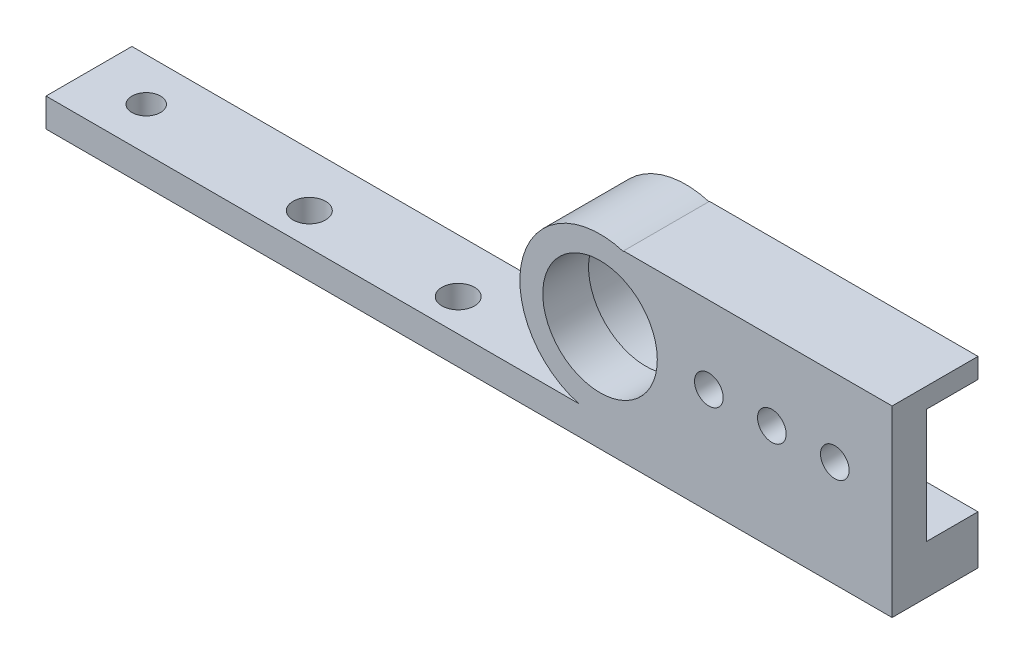
SolidWorks part; units mm, degrees
ref_plane "前视基准面" through (0, 0, 0) normal (0, 0, 1) x (1, 0, 0)
ref_plane "上视基准面" through (0, 0, 0) normal (0, 1, 0) x (1, 0, 0)
ref_plane "右视基准面" through (0, 0, 0) normal (1, 0, 0) x (0, 0, -1)
sketch "草图1" plane through (0, 0, 0) normal (0, 0, 1) x (1, 0, 0)
  line L1 (20, -10) -> (-20, -10)
  line L2 (20, -10) -> (20, 10)
  line L3 (20, 10) -> (-20, 10)
  line L4 (-20, -10) -> (-20, 10)
  line L5 (20, -10) -> (-20, 10) construction
  line L6 (20, 10) -> (-20, -10) construction
  point P0 (0, 0)
  dimension "D1" = 40
  dimension "D2" = 20
extrude "凸台-拉伸1" add sketch "草图1" along normal blind 6
sketch "草图2" plane through (0, 0, 6) normal (0, 0, 1) x (1, 0, 0)
  line L0 (20, -10) -> (20, 10) construction
  circle A0 centre (10, 0) radius 2.5
  circle A1 centre (-1, 0) radius 2.5
  circle A2 centre (-12, 0) radius 2.5
  dimension "D1" = 10
  dimension "D2" = 5
  dimension "D3" = 3
extrude "切除-拉伸1" cut sketch "草图2" against normal through all
sketch "草图3" plane through (0, 0, 6) normal (0, 0, 1) x (1, 0, 0)
  line L0 (20, 13.5) -> (20, 10)
  line L1 (20, -13.5) -> (-26.894, -13.5)
  line L3 (20, 13.5) -> (-26.894, 13.5)
  line L4 (-20, 10) -> (-20, -10)
  line L5 (-20, -10) -> (20, -10)
  line L6 (20, -10) -> (20, 10)
  line L7 (20, 10) -> (-20, 10)
  line L8 (-20, 10) -> (-20, -10)
  line L9 (-20, -10) -> (20, -10)
  line L10 (20, -10) -> (20, 10)
  line L11 (20, 10) -> (-20, 10)
  line L12 (-26.894, -13.5) -> (-26.894, 13.5)
  line L13 (20, -10.0394) -> (-26.894, 13.5) construction
  line L14 (20, 10.0394) -> (-26.894, -13.5) construction
  line L15 (20, -10) -> (20, -13.5)
  circle A0 centre (-31, 0) radius 11
  circle A1 centre (-31, 0) radius 14
  point P2 (0, 0)
  line M10 (-20, 10) -> (-20, -10)
  line M11 (-20, -10) -> (20, -10)
  line M13 (20, 10) -> (-20, 10)
  dimension "D3" = 22
  dimension "D4" = 28
  dimension "D2" = 3.5
  dimension "D1" = 0
extrude "凸台-拉伸2" add sketch "草图3" against normal blind 15 contours L3 A1 L1 L12 A0 | A1 L1 L15 M11 M10 | L1 A1 L8 A0 L12 | L8 A1 L3 L12 A0 | L8 A1 | A1 L0 L3 M10 M13 region at (-1.9449, 11.7771, 6) region at (-1.9449, -11.7771, 6) region at (-23.0173, 9.0328, 6) region at (-27.2274, 11.7946, 6) region at (-18.7882, 0, 6) region at (-23.0173, -9.0328, 6)
sketch "草图5" plane through (0, 0, 6) normal (0, 0, 1) x (1, 0, 0)
  circle A0 centre (-31, 0) radius 10
  circle A1 centre (-31, 0) radius 11 construction
  circle A2 centre (-31, 0) radius 11
  dimension "D1" = 20
extrude "凸台-拉伸3" add sketch "草图5" against normal blind 8
sketch "草图6" plane through (0, 0, 6) normal (0, 0, 1) x (1, 0, 0)
  circle A0 centre (-31, 0) radius 8.5
  circle A1 centre (-31, 0) radius 10 construction
  circle A2 centre (-31, 0) radius 10
  dimension "D1" = 17
sketch "草图9" plane through (0, -13.5, 0) normal (0, -1, 0) x (1, 0, 0)
  circle A0 centre (-18.2368, -1.344) radius 5.5352
sketch "草图10" plane through (20, 0, 0) normal (1, 0, 0) x (0, 0, -1)
  line L1 (9, -13.5) -> (-6, -13.5)
  line L2 (9, -13.5) -> (9, -18.5)
  line L3 (9, -18.5) -> (-6, -18.5)
  line L4 (-6, -13.5) -> (-6, -18.5)
  dimension "D1" = 5
extrude "凸台-拉伸4" add sketch "草图10" against normal blind 200
sketch "草图11" plane through (0, 0, 6) normal (0, 0, 1) x (1, 0, 0)
  line L1 (-28.6193, -11.8661) -> (-25.5243, -11.8661)
  line L2 (-28.6193, -11.8661) -> (-28.6193, -14.961)
  line L3 (-28.6193, -14.961) -> (-25.5243, -14.961)
  line L4 (-25.5243, -11.8661) -> (-25.5243, -14.961)
extrude "凸台-拉伸5" add sketch "草图11" against normal through all
sketch "草图13" plane through (0, -18.5, 0) normal (0, -1, 0) x (1, 0, 0)
  line L0 (-164.0842, 6) -> (-164.0842, -9)
  line L1 (-180, 6) -> (20, 6) construction
  line L2 (-164.0842, 123.2983) -> (-164.0842, -246.7017) construction
  line L3 (-180, -9) -> (20, -9) construction
sketch "草图14" plane through (0, -18.5, 0) normal (0, -1, 0) x (1, 0, 0)
  line L0 (-127.7451, -15.7251) -> (-127.7451, 9.3691)
  line L1 (-127.7451, 125.09) -> (-127.7451, -244.91) construction
sketch "草图15" plane through (0, -18.5, 0) normal (0, -1, 0) x (1, 0, 0)
  line L1 (-127.7451, -15.7251) -> (-184.1416, -15.7251)
  line L2 (-127.7451, -15.7251) -> (-127.7451, 11.9644)
  line L3 (-127.7451, 11.9644) -> (-184.1416, 11.9644)
  line L4 (-184.1416, -15.7251) -> (-184.1416, 11.9644)
sketch "草图16" plane through (0, -18.5, 0) normal (0, -1, 0) x (1, 0, 0)
  line L0 (-127.7451, -17.1171) -> (-127.7451, 37.1771)
  line L1 (-127.7451, 125.09) -> (-127.7451, -244.91) construction
sketch "草图17" plane through (0, -18.5, 0) normal (0, -1, 0) x (1, 0, 0)
  line L1 (-127.7451, -17.1171) -> (-191.9094, -17.1171)
  line L2 (-127.7451, -17.1171) -> (-127.7451, 25.2398)
  line L3 (-127.7451, 25.2398) -> (-191.9094, 25.2398)
  line L4 (-191.9094, -17.1171) -> (-191.9094, 25.2398)
extrude "切除-拉伸2" cut sketch "草图17" against normal through all
sketch "草图20" plane through (0, -18.5, 0) normal (0, -1, 0) x (1, 0, 0)
  line L0 (-127.7451, 6) -> (-127.7451, -9) construction
  line L1 (-127.7451, -1.5) -> (-117.7451, -1.5) construction
  circle A0 centre (-117.7451, -1.5) radius 2.5
  dimension "D1" = 5
  dimension "D2" = 10
extrude "切除-拉伸3" cut sketch "草图20" against normal through all
sketch "草图21" plane through (0, -18.5, 0) normal (0, -1, 0) x (1, 0, 0)
  circle A0 centre (-87.421, 0.3438) radius 2.8371
  circle A1 centre (-61.421, 0.3438) radius 2.8371
extrude "切除-拉伸4" cut sketch "草图21" against normal through all
